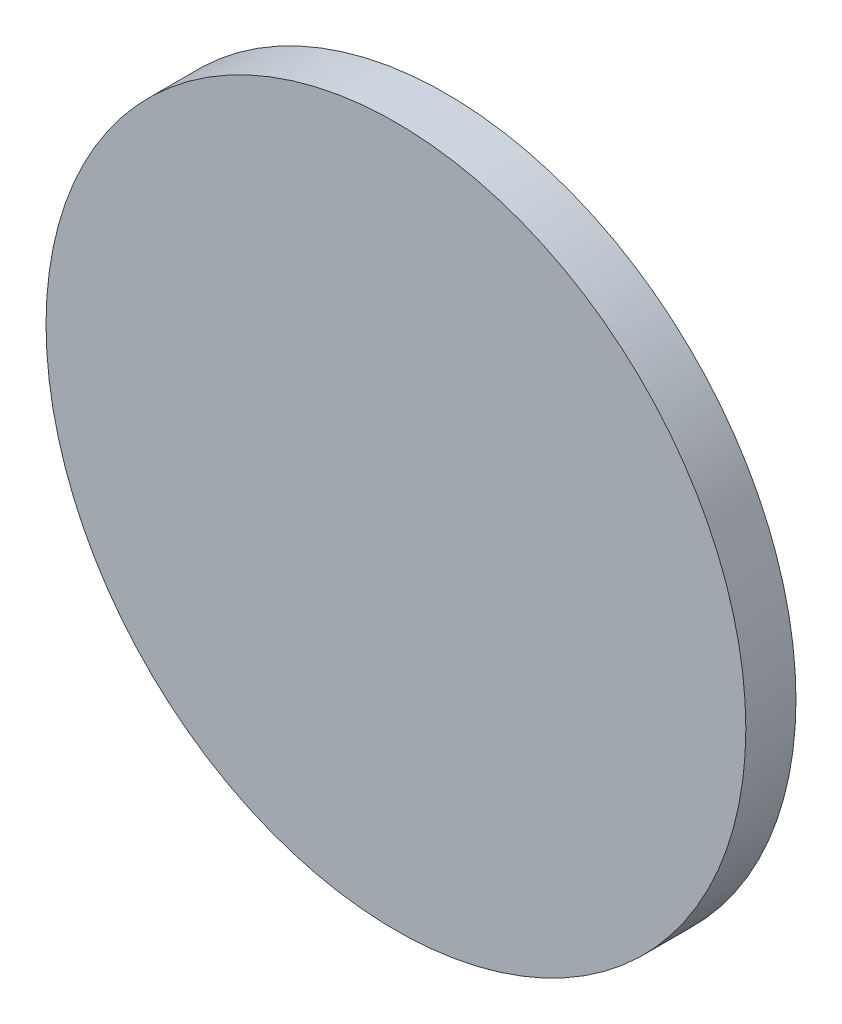
SolidWorks part; units mm, degrees
ref_plane "Plan de face" through (0, 0, 0) normal (0, 0, 1) x (1, 0, 0)
ref_plane "Plan de dessus" through (0, 0, 0) normal (0, 1, 0) x (1, 0, 0)
ref_plane "Plan de droite" through (0, 0, 0) normal (1, 0, 0) x (0, 0, -1)
sketch "Esquisse1" plane through (0, 0, 0) normal (0, 0, 1) x (1, 0, 0)
  circle A0 centre (0, 0) radius 34.9
  dimension "D1" = 69.8
extrude "Boss.-Extru.1" add sketch "Esquisse1" along normal blind 5
